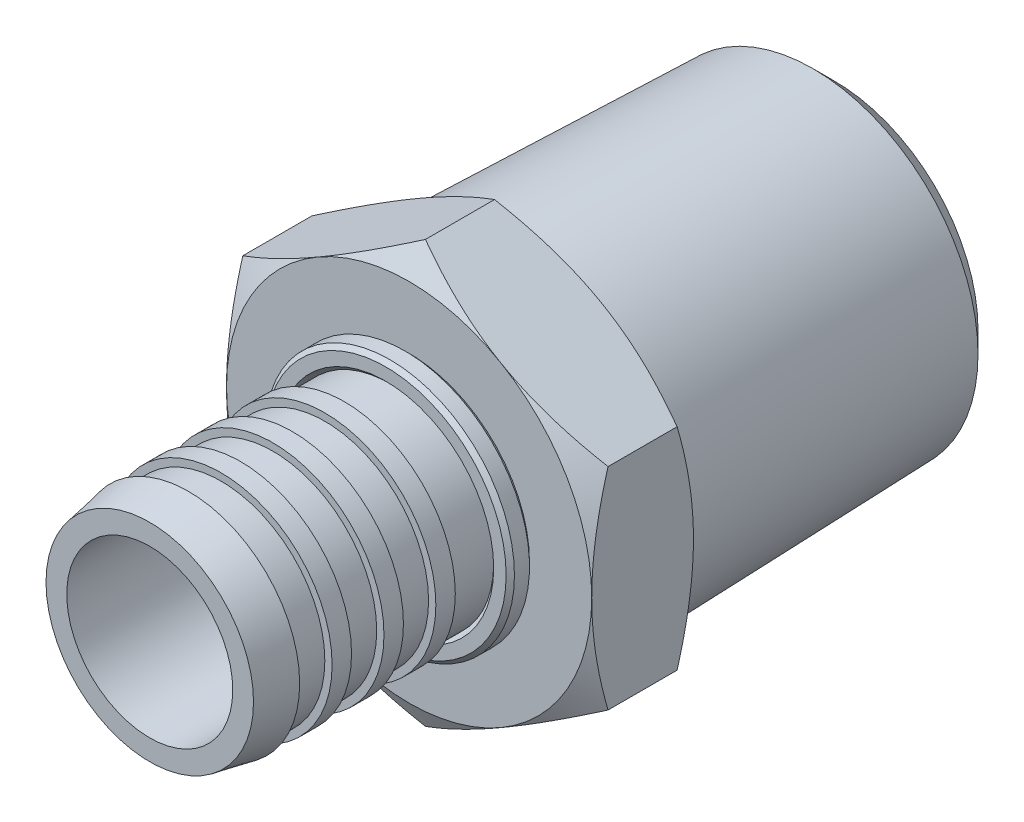
SolidWorks part; units mm, degrees
ref_plane "Front" through (0, 0, 0) normal (0, 0, 1) x (1, 0, 0)
ref_plane "Top" through (0, 0, 0) normal (0, 1, 0) x (1, 0, 0)
ref_plane "Right" through (0, 0, 0) normal (1, 0, 0) x (0, 0, -1)
sketch "Sketch1" plane through (0, 0, 0) normal (1, 0, 0) x (0, 0, -1)
  line L0 (-18.5737, 6.35) -> (-16.5894, 6.35)
  line L1 (-5.08, 8.001) -> (-1.9685, 8.001) construction
  line L2 (-5.08, 11.176) -> (1.143, 11.176)
  line L3 (20.955, 8.001) -> (20.955, 10.0512)
  line L5 (-20.955, 5.08) -> (-20.955, 6.35)
  line L6 (-20.955, 5.08) -> (-3.5242, 5.08)
  line L7 (-3.5242, 5.08) -> (-1.9685, 8.001)
  line L8 (1.143, 10.668) -> (20.955, 10.0512)
  line L9 (-20.955, 6.35) -> (-20.955, -6.35) construction
  line L10 (20.955, 8.001) -> (-1.9685, 8.001)
  line L11 (-12.2396, 5.08) -> (-12.2396, -5.08) construction
  line L13 (-1.9685, 11.176) -> (-1.9685, -11.176) construction
  line L14 (15.008, 0) -> (-15.008, 0) construction
  line L15 (-20.955, 6.35) -> (-18.5737, 6.7945)
  line L16 (-18.5737, 6.7945) -> (-18.5737, 6.35)
  line L17 (-16.5894, 6.35) -> (-16.5894, 6.7945)
  line L18 (-16.5894, 6.7945) -> (-15.3987, 6.7945)
  line L19 (-15.3987, 6.7945) -> (-15.3987, 6.35)
  line L20 (-13.4144, 6.35) -> (-13.4144, 6.7945)
  line L21 (-13.4144, 6.7945) -> (-12.2237, 6.7945)
  line L22 (-12.2237, 6.7945) -> (-12.2237, 6.35)
  line L23 (-15.3987, 6.35) -> (-13.4144, 6.35)
  line L24 (-12.2237, 6.35) -> (-10.2394, 6.35)
  line L25 (-16.5894, 6.35) -> (-15.3987, 6.35) construction
  line L26 (-13.4144, 6.35) -> (-12.2237, 6.35) construction
  line L27 (-18.5737, 6.7945) -> (-18.5737, -6.7945) construction
  line L28 (-18.5737, 6.35) -> (-19.7644, 6.35) construction
  line L29 (-19.7644, 6.35) -> (-20.955, 6.35) construction
  line L30 (-20.955, 0) -> (20.955, 0) construction
  line L32 (-3.5242, 5.08) -> (-3.5242, 8.001) construction
  line L33 (-5.08, 11.176) -> (-5.08, 6.35)
  line L35 (-10.2394, 6.35) -> (-10.2394, 6.7945)
  line L36 (-10.2394, 6.7945) -> (-9.0487, 6.7945)
  line L37 (1.143, 11.176) -> (1.143, 10.668)
  line L38 (1.143, 10.668) -> (1.143, -10.668) construction
  line L39 (20.955, 8.001) -> (20.955, -8.001) construction
  line L40 (-9.0487, 6.7945) -> (-9.0487, 6.35)
  line L41 (-9.0487, 6.35) -> (-5.08, 6.35)
  point P14 (-20.955, 0)
  point P18 (-12.2396, 0)
  point P21 (1.143, 0)
  point P32 (-18.5738, 0)
  point P45 (-1.9685, 0)
  dimension "D4" = 13.589
  dimension "D2" = 2.3813
  dimension "D5" = 10.16
  dimension "D3" = 1.783
  dimension "D6" = 16.002
  dimension "Insertion Lg" = 15.875
  dimension "L4" = 19.812
  dimension "D1" = 3.9688
revolve "Revolve1" add sketch "Sketch1" angle 360 about L30
sketch "Sketch16" plane through (0, 0, -1.143) normal (0, 0, -1) x (-1, 0, 0)
  circle A1 centre (0, 0) radius 11.176
  circle A2 centre (0, 0) radius 11.176
  dimension "D1" = 0
extrude "Cut-Extrude4" cut sketch "Sketch16" along normal through all
sketch "Sketch17" plane through (0, 0, 0) normal (1, 0, 0) x (0, 0, -1)
  line L0 (20.955, 8.001) -> (-1.9685, 8.001) construction
  line L1 (20.955, 8.001) -> (20.955, 10.0512) construction
  line L2 (1.143, 10.668) -> (20.955, 10.0512) construction
  line L3 (1.143, 11.176) -> (1.143, 10.668) construction
  line L4 (20.955, 8.001) -> (1.143, 8.001)
  line L5 (20.955, 8.001) -> (20.955, 10.0512)
  line L6 (1.143, 10.668) -> (20.955, 10.0512)
  line L7 (1.143, 8.001) -> (1.143, 10.668)
revolve "Revolve2" add sketch "Sketch17" angle 360 about L30
sketch "Sketch14" plane through (0, 0, -1.143) normal (0, 0, -1) x (-1, 0, 0)
  circle A1 centre (0, 0) radius 10.668
curve "Helix/Spiral1"
sketch "Sketch13" plane through (0, 0, 0) normal (1, 0, 0) x (0, 0, -1)
  line L7 (-0.5579, 10.8644) -> (1.2564, 10.8644) construction
  line L8 (-0.5579, 10.8644) -> (0.3493, 9.2932) construction
  line L9 (0.3493, 9.2932) -> (1.2564, 10.8644) construction
  line L10 (0.3493, 10.8644) -> (0.3493, 10.668) construction
  line L11 (0.3493, 9.2932) -> (0.3493, 9.4896) construction
  line L12 (0.2359, 9.4896) -> (0.4626, 9.4896) construction
  line L13 (-0.4445, 10.668) -> (1.143, 10.668) construction
  line L14 (0.3493, 10.7662) -> (1.1997, 10.7662) construction
  line L15 (1.1997, 10.7662) -> (-0.5579, 10.8644)
  line L16 (-0.5579, 10.8644) -> (0.2359, 9.4896)
  line L17 (0.2359, 9.4896) -> (0.4626, 9.4896)
  line L18 (0.4626, 9.4896) -> (1.1997, 10.7662)
  dimension "D5" = 1.8143
  dimension "D6" = 0.2268
chamfer "Chamfer1" distance 1.27 angle 45 1 edges at (10.0512, 0, -20.955) first distance on face at (10.0512, 0, -20.955)
sweep "Cut-Sweep1" [suppressed] cut profiles "Sketch13" path "Helix/Spiral1"
sketch "Sketch10" plane through (0, 0, -1.143) normal (0, 0, -1) x (-1, 0, 0)
  line L1 (11.176, 6.4525) -> (0, 12.9049)
  line L2 (0, 12.9049) -> (-11.176, 6.4525)
  line L3 (-11.176, 6.4525) -> (-11.176, -6.4525)
  line L4 (-11.176, -6.4525) -> (0, -12.9049)
  line L5 (0, -12.9049) -> (11.176, -6.4525)
  line L6 (11.176, -6.4525) -> (11.176, 6.4525)
  circle A2 centre (0, 0) radius 11.176 construction
  circle A3 centre (0, 0) radius 8.001 construction
  circle A4 centre (0, 0) radius 8.001
  dimension "D1" = 22.352
extrude "Boss-Extrude1" add sketch "Sketch10" against normal up to surface (6.223 mm away) up to face at (6.35, 0, 5.08)
sketch "Sketch11" plane through (0, 0, -1.143) normal (0, 0, -1) x (-1, 0, 0)
  circle A1 centre (0, 0) radius 11.176 construction
  circle A2 centre (0, 0) radius 11.176
extrude "Cut-Extrude1" cut sketch "Sketch11" against normal through all draft 60 flip side to cut
sketch "Sketch12" plane through (0, 0, 5.08) normal (0, 0, -1) x (-1, 0, 0)
  circle A2 centre (0, 0) radius 11.176
  circle A3 centre (0, 0) radius 11.176
  dimension "D1" = 0
extrude "Cut-Extrude2" cut sketch "Sketch12" along normal through all draft 60 flip side to cut
sketch "Sketch18" plane through (0, 0, 0) normal (1, 0, 0) x (0, 0, -1)
  line L0 (0, 0) -> (-20.955, 0) construction
  line L1 (-6.5087, 7.62) -> (-5.08, 7.62)
  line L2 (-6.5087, 7.62) -> (-6.5087, 6.35)
  line L3 (-6.5087, 6.35) -> (-5.08, 6.35)
  line L4 (-5.08, 7.62) -> (-5.08, 6.35)
  line L5 (-20.955, 6.35) -> (-20.955, -6.35) construction
  dimension "D1" = 1.4288
  dimension "D2" = 15.24
revolve "Revolve3" add sketch "Sketch18" angle 360 about L0
chamfer "Chamfer2" distance 0.254 angle 45 4 edges at (-7.62, 0, 5.08) (-7.62, 0, 6.5087) (-6.35, 0, 6.5087) (-6.35, 0, 5.08)
combine bodies "Combine1" operation type add bodies to combine 117 121
equation "\"D4@Sketch1\" = \"Tube size@Sketch1\" * 1.07"
equation "\"D2@Sketch1\"=\"Insertion Lg@Sketch1\" * .15"
equation "\"D5@Sketch1\" = \"Tube size@Sketch1\" * .8"
equation "\"D6@Sketch1\" = \"Pipe OD@Sketch1\" * .75"
equation "\"D3@Helix/Spiral1\" = \"Lg@Sketch1\" * .5"
equation "\"D1@Chamfer1\" = \"D4@Helix/Spiral1\" * .7"
equation "\"D1@Sketch10\"=\"Hex@Sketch1\""
equation "\"D1@Sketch1\"=\"Insertion Lg@Sketch1\"/4"
equation "\"D2@Sketch18\"=\"Tube size@Sketch1\"*1.2"
equation "\"D1@Sketch18\"=\"D2@Sketch1\"*.6"
equation "\"D5@Sketch13\"=\"D4@Helix/Spiral1\""
equation "\"D6@Sketch13\"=\"D5@Sketch13\"/8"
